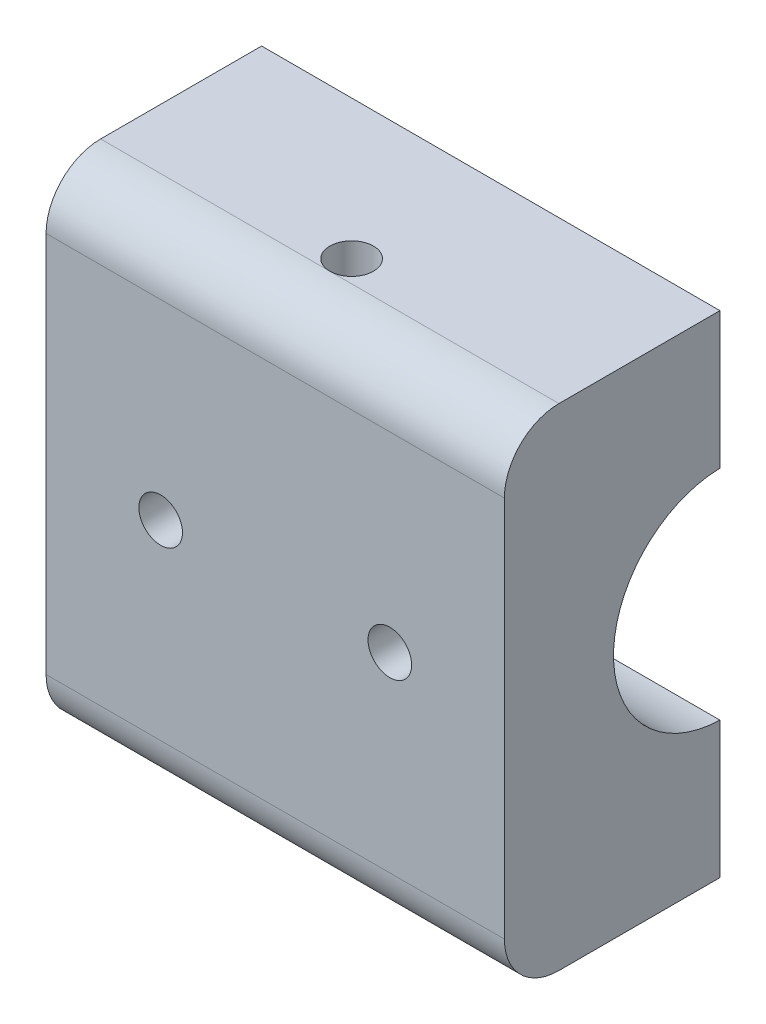
SolidWorks part; units mm, degrees
material "Custom Plastic"
ref_plane "Front Plane" through (0, 0, 0) normal (0, 0, 1) x (1, 0, 0)
ref_plane "Top Plane" through (0, 0, 0) normal (0, 1, 0) x (1, 0, 0)
ref_plane "Right Plane" through (0, 0, 0) normal (1, 0, 0) x (0, 0, -1)
sketch "Sketch1" plane through (0, 0, 0) normal (1, 0, 0) x (0, 0, -1)
  line L0 (0, 22.5) -> (0, -22.5) construction
  line L1 (-0.25, 22.5) -> (-0.25, 9.9969)
  line L2 (-0.25, -9.9969) -> (-0.25, -22.5)
  line L4 (-0.25, 22.5) -> (-0.25, -22.5) construction
  line L6 (-20, 17.5) -> (-20, -17.5)
  line L8 (0, 22.5) -> (-15, 22.5)
  line L10 (0, 0) -> (-20, 0) construction
  line L12 (0, -22.5) -> (-15, -22.5)
  arc A1 (0, 10) -> (0, -10) centre (0, 0) ccw
  circle A3 centre (0, 0) radius 10 construction
  arc A4 (-15, 22.5) -> (-20, 17.5) centre (-15, 17.5) ccw
  arc A5 (-20, -17.5) -> (-15, -22.5) centre (-15, -17.5) ccw
  point P23 (-10, 0)
  dimension "D2" = 45
  dimension "D4" = 5
  dimension "D3" = 20
  dimension "D1" = 0.25
extrude "Boss-Extrude1" add sketch "Sketch1" against normal blind 42 contours A1 L1 L2 region at (0, 0, 11.1992)
sketch "Sketch4" plane through (0, 0, 20) normal (0, 0, 1) x (1, 0, 0)
  circle A0 centre (-10.5, 0) radius 2
  circle A1 centre (-31.5, 0) radius 2
  circle A2 centre (-10.5, 0) radius 2 construction
extrude "Cut-Extrude4" cut sketch "Sketch4" against normal through all
sketch "Sketch5" plane through (0, -22.5, 0) normal (0, -1, 0) x (1, 0, 0)
  line L0 (-21, 20) -> (-21, 0.25) construction
  line L3 (-42, 20) -> (0, 20) construction
  line L4 (-42, 0.25) -> (0, 0.25) construction
  line L5 (-42, 15) -> (0, 15) construction
  circle A0 centre (-21, 13) radius 2
  dimension "D1" = 4
extrude "Cut-Extrude5" cut sketch "Sketch5" against normal through all
